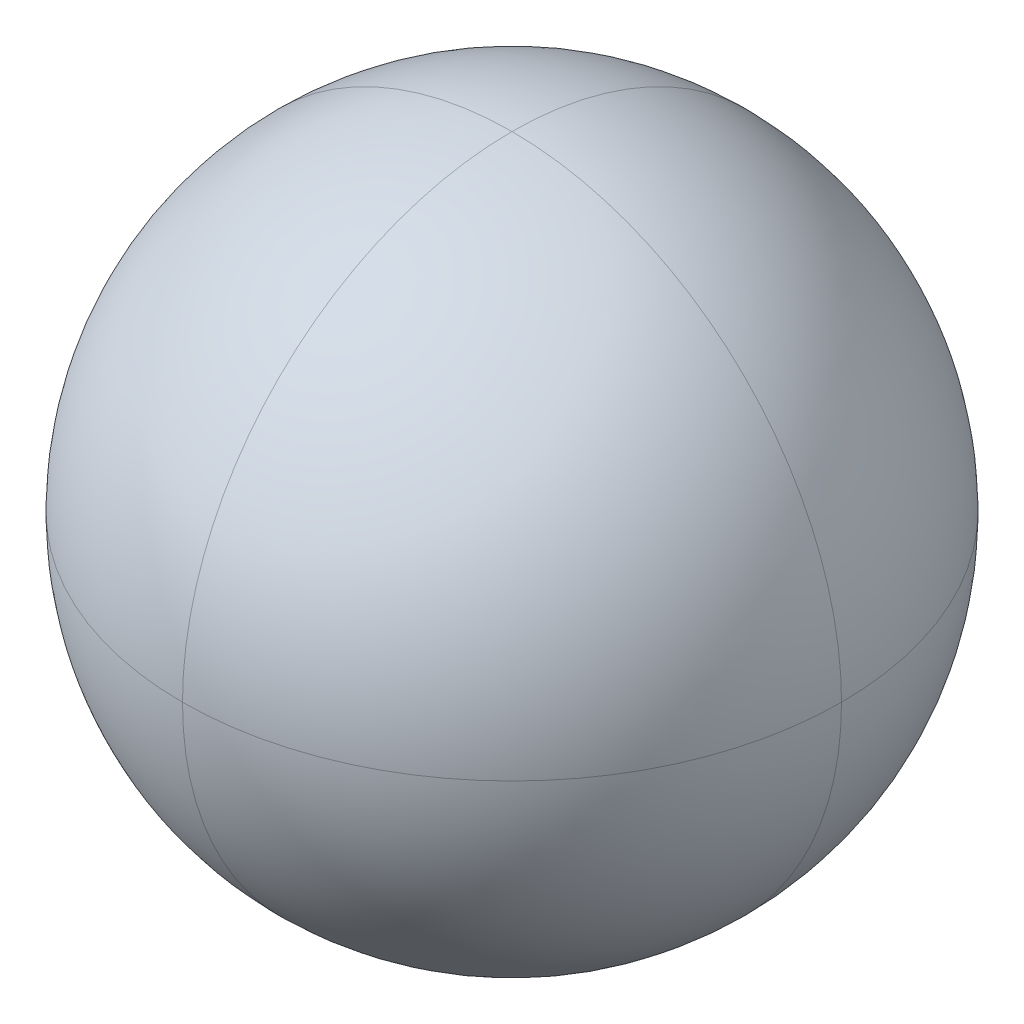
SolidWorks part; units mm, degrees
ref_plane "Front Plane" through (0, 0, 0) normal (0, 0, 1) x (1, 0, 0)
ref_plane "Top Plane" through (0, 0, 0) normal (0, 1, 0) x (1, 0, 0)
ref_plane "Right Plane" through (0, 0, 0) normal (1, 0, 0) x (0, 0, -1)
sketch "Sketch1" plane through (0, 0, 0) normal (0, 0, 1) x (1, 0, 0)
  line L1 (-19.685, -19.685) -> (19.685, -19.685)
  line L2 (-19.685, -19.685) -> (-19.685, 19.685)
  line L3 (-19.685, 19.685) -> (19.685, 19.685)
  line L4 (19.685, -19.685) -> (19.685, 19.685)
  line L5 (-19.685, -19.685) -> (19.685, 19.685) construction
  line L6 (-19.685, 19.685) -> (19.685, -19.685) construction
  point P0 (0, 0)
  dimension "D1" = 39.37
  dimension "D2" = 39.37
extrude "Boss-Extrude1" add sketch "Sketch1" along normal blind 39.37
fillet "Fillet4" radius 19.685 12 edges at (-19.685, 0, 39.37) (0, -19.685, 39.37) (19.685, 0, 39.37) (0, -19.685, 0) (-19.685, 0, 0) (0, 19.685, 0) (19.685, 0, 0) (0, 19.685, 39.37) (19.685, -19.685, 19.685) (-19.685, -19.685, 19.685) (-19.685, 19.685, 19.685) (19.685, 19.685, 19.685)
